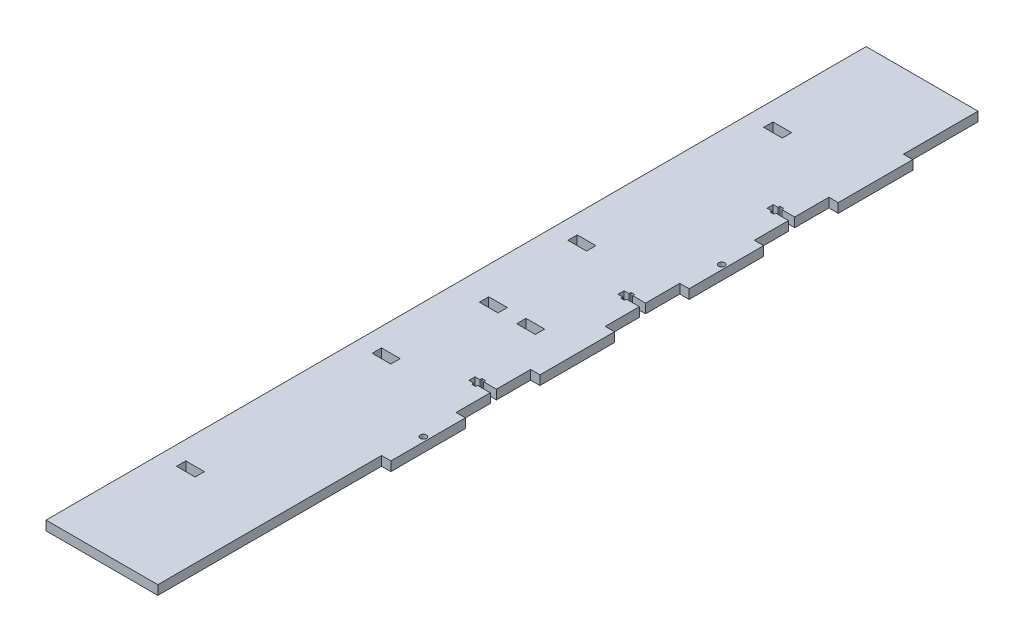
SolidWorks part; units mm, degrees
ref_plane "Front Plane" through (0, 0, 0) normal (0, 0, 1) x (1, 0, 0)
ref_plane "Top Plane" through (0, 0, 0) normal (0, 1, 0) x (1, 0, 0)
ref_plane "Right Plane" through (0, 0, 0) normal (1, 0, 0) x (0, 0, -1)
sketch "Sketch1" plane through (0, 0, 0) normal (0, 0, 1) x (1, 0, 0)
  line L1 (38.1, 38.1) -> (-38.1, 38.1)
  line L2 (38.1, 38.1) -> (38.1, 44.45)
  line L3 (38.1, 44.45) -> (-38.1, 44.45)
  line L4 (-38.1, 38.1) -> (-38.1, 44.45)
  dimension "D1" = 6.35
extrude "Boss-Extrude1" add sketch "Sketch1" along normal blind 558.8
sketch "Sketch2" plane through (0, 44.45, 0) normal (0, 1, 0) x (1, 0, 0)
  line L0 (0, -558.8) -> (0, 0) construction
  line L1 (38.1, -558.8) -> (-38.1, -558.8) construction
  line L2 (0, -279.4) -> (-28.148, -279.4) construction
  line L4 (19.05, -282.575) -> (6.35, -282.575)
  line L5 (19.05, -282.575) -> (19.05, -276.225)
  line L6 (19.05, -276.225) -> (6.35, -276.225)
  line L7 (6.35, -282.575) -> (6.35, -276.225)
  line L8 (-6.35, -282.575) -> (-19.05, -282.575)
  line L9 (-6.35, -282.575) -> (-6.35, -276.225)
  line L10 (-6.35, -276.225) -> (-19.05, -276.225)
  line L11 (-19.05, -282.575) -> (-19.05, -276.225)
  dimension "D1" = 6.35
  dimension "D2" = 6.35
  dimension "D3" = 12.7
  dimension "D4" = 12.7
  dimension "D5" = 12.7
extrude "Cut-Extrude1" cut sketch "Sketch2" against normal through all
sketch "Sketch3" plane through (38.1, 0, 0) normal (1, 0, 0) x (0, 0, -1)
  line L0 (-558.8, 38.1) -> (0, 38.1) construction
  line L1 (-406.4, 38.1) -> (-355.6, 38.1)
  line L2 (-406.4, 38.1) -> (-406.4, 44.45)
  line L3 (-406.4, 44.45) -> (-355.6, 44.45)
  line L4 (-355.6, 38.1) -> (-355.6, 44.45)
  line L5 (-558.8, 44.45) -> (0, 44.45) construction
  line L6 (-355.6, 38.1) -> (-355.6, 44.45) construction
  line L7 (-406.4, 44.45) -> (-406.4, 38.1) construction
  line L8 (-304.8, 44.45) -> (-304.8, 38.1) construction
  line L9 (-304.8, 44.45) -> (-254, 44.45)
  line L10 (-304.8, 44.45) -> (-304.8, 38.1)
  line L11 (-304.8, 38.1) -> (-254, 38.1)
  line L12 (-254, 44.45) -> (-254, 38.1)
  line L13 (-203.2, 44.45) -> (-203.2, 38.1) construction
  line L14 (-203.2, 44.45) -> (-152.4, 44.45)
  line L15 (-203.2, 44.45) -> (-203.2, 38.1)
  line L16 (-203.2, 38.1) -> (-152.4, 38.1)
  line L17 (-152.4, 44.45) -> (-152.4, 38.1)
  line L18 (-101.6, 44.45) -> (-101.6, 38.1) construction
  line L19 (-101.6, 44.45) -> (-50.8, 44.45)
  line L20 (-101.6, 44.45) -> (-101.6, 38.1)
  line L21 (-101.6, 38.1) -> (-50.8, 38.1)
  line L22 (-50.8, 44.45) -> (-50.8, 38.1)
  line L23 (-254, 38.1) -> (-254, 44.45) construction
  line L24 (-152.4, 38.1) -> (-152.4, 44.45) construction
  line L25 (-101.6, 38.1) -> (-50.8, 38.1) construction
  line L26 (-50.8, 38.1) -> (-50.8, 44.45) construction
extrude "Boss-Extrude2" add sketch "Sketch3" along normal up to surface (6.35 mm away)
sketch "Sketch4" plane through (0, 44.45, 0) normal (0, 1, 0) x (1, 0, 0)
  line L0 (-38.1, -558.8) -> (-38.1, 0) construction
  line L1 (-12.7, -482.6) -> (-25.4, -482.6)
  line L2 (-12.7, -482.6) -> (-12.7, -476.25)
  line L3 (-12.7, -476.25) -> (-25.4, -476.25)
  line L4 (-25.4, -482.6) -> (-25.4, -476.25)
  line L5 (38.1, -558.8) -> (-38.1, -558.8) construction
  dimension "D1" = 6.35
  dimension "D2" = 12.7
  dimension "D3" = 12.7
  dimension "D4" = 76.2
extrude "Cut-Extrude2" cut sketch "Sketch4" against normal through all
pattern_linear "LPattern1" count 4 spacing 133.35 along (0, 0, -1) of "Cut-Extrude2"
sketch "Sketch5" plane through (0, 38.1, 0) normal (0, -1, 0) x (1, 0, 0)
  line L0 (38.1, 383.0955) -> (44.45, 378.9045) construction
  line L1 (44.45, 355.6) -> (44.45, 406.4) construction
  line L2 (38.1, 378.9045) -> (44.45, 383.0955) construction
  line L3 (38.1, 179.8955) -> (44.45, 175.7045) construction
  line L4 (44.45, 152.4) -> (44.45, 203.2) construction
  line L5 (38.1, 175.7045) -> (44.45, 179.8955) construction
  line L6 (38.1, 330.2) -> (17.295, 330.2) construction
  line L7 (38.1, 355.6) -> (38.1, 304.8) construction
  line L8 (38.1, 228.6) -> (21.8949, 228.6) construction
  line L9 (38.1, 254) -> (38.1, 203.2) construction
  line L10 (38.1, 127) -> (16.6562, 127) construction
  line L11 (38.1, 152.4) -> (38.1, 101.6) construction
  circle A0 centre (41.275, 381) radius 2.0955
  circle A1 centre (41.275, 177.8) radius 2.0955
  line B0 (38.1, 328.1045) -> (38.1, 332.2955)
  line B1 (26.797, 332.2955) -> (26.797, 333.629)
  line B2 (26.797, 333.629) -> (29.337, 333.629)
  line B3 (29.337, 333.629) -> (29.337, 332.2955)
  line B4 (29.337, 332.2955) -> (38.1, 332.2955)
  line B5 (26.797, 332.2955) -> (23.495, 332.2955)
  line B6 (23.495, 332.2955) -> (23.495, 328.1045)
  line B7 (26.797, 328.1045) -> (23.495, 328.1045)
  line B8 (29.337, 328.1045) -> (38.1, 328.1045)
  line B9 (29.337, 326.771) -> (29.337, 328.1045)
  line B10 (26.797, 326.771) -> (29.337, 326.771)
  line B11 (26.797, 328.1045) -> (26.797, 326.771)
  line B12 (38.1, 124.9045) -> (38.1, 129.0955)
  line B13 (26.797, 129.0955) -> (26.797, 130.429)
  line B14 (26.797, 130.429) -> (29.337, 130.429)
  line B15 (29.337, 130.429) -> (29.337, 129.0955)
  line B16 (29.337, 129.0955) -> (38.1, 129.0955)
  line B17 (26.797, 129.0955) -> (23.495, 129.0955)
  line B18 (23.495, 129.0955) -> (23.495, 124.9045)
  line B19 (26.797, 124.9045) -> (23.495, 124.9045)
  line B20 (29.337, 124.9045) -> (38.1, 124.9045)
  line B21 (29.337, 123.571) -> (29.337, 124.9045)
  line B22 (26.797, 123.571) -> (29.337, 123.571)
  line B23 (26.797, 124.9045) -> (26.797, 123.571)
  line B24 (38.1, 127) -> (23.495, 127) construction
  line B25 (28.067, 130.429) -> (28.067, 120.3352) construction
  line B26 (38.1, 226.5045) -> (38.1, 230.6955)
  line B27 (26.797, 230.6955) -> (26.797, 232.029)
  line B28 (26.797, 232.029) -> (29.337, 232.029)
  line B29 (29.337, 232.029) -> (29.337, 230.6955)
  line B30 (29.337, 230.6955) -> (38.1, 230.6955)
  line B31 (26.797, 230.6955) -> (23.495, 230.6955)
  line B32 (23.495, 230.6955) -> (23.495, 226.5045)
  line B33 (26.797, 226.5045) -> (23.495, 226.5045)
  line B34 (29.337, 226.5045) -> (38.1, 226.5045)
  line B35 (29.337, 225.171) -> (29.337, 226.5045)
  line B36 (26.797, 225.171) -> (29.337, 225.171)
  line B37 (26.797, 226.5045) -> (26.797, 225.171)
  dimension "D1" = 4.191
  dimension "D2" = 4.191
sketch_block_instance "TSlot-1"
sketch_block "TSlot" parameters "D1"=3.302, "D2"=2.54, "D3"=3.175, "D4"=8.763, "D5"=1.3462
sketch_block_instance "TSlot-3"
sketch_block_instance "TSlot-4"
extrude "Cut-Extrude3" cut sketch "Sketch5" against normal through all
